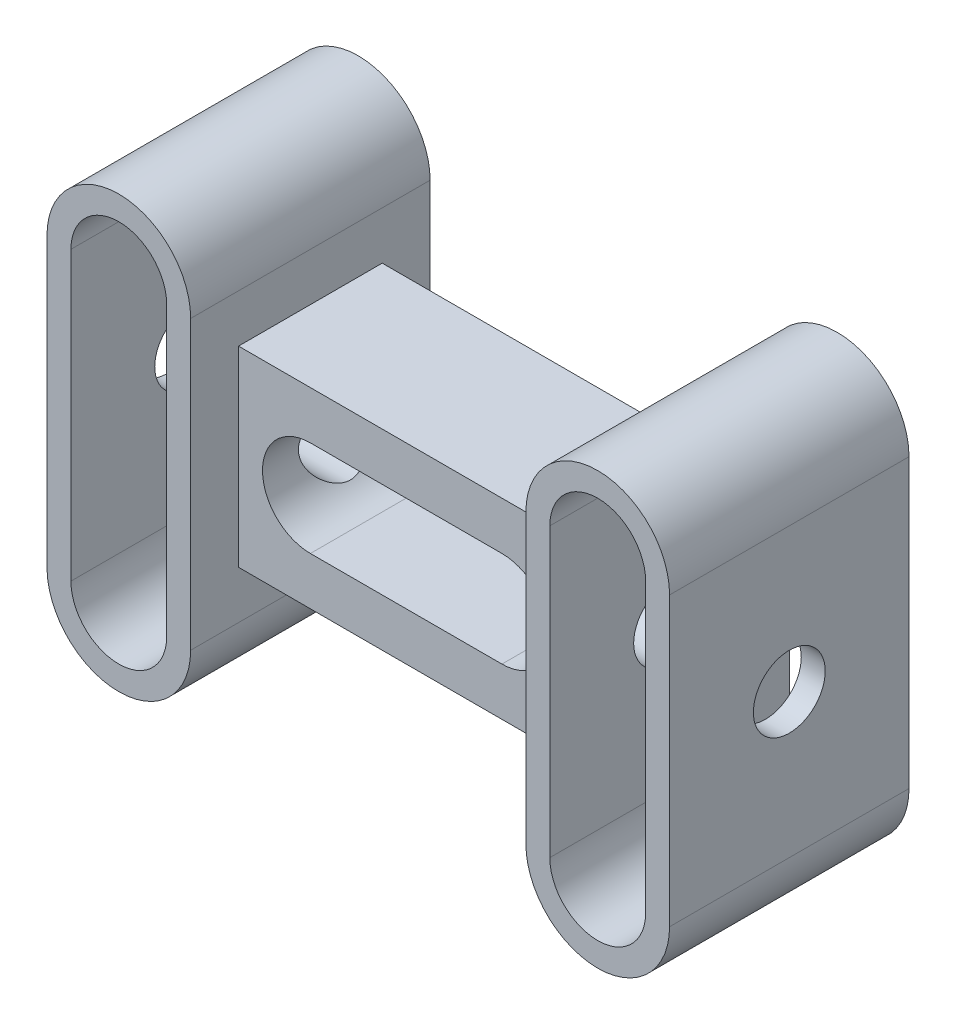
SolidWorks part; units mm, degrees
ref_plane "Front Plane" through (0, 0, 0) normal (0, 0, 1) x (1, 0, 0)
ref_plane "Top Plane" through (0, 0, 0) normal (0, 1, 0) x (1, 0, 0)
ref_plane "Right Plane" through (0, 0, 0) normal (1, 0, 0) x (0, 0, -1)
sketch "Sketch1" plane through (0, 0, 0) normal (0, 0, 1) x (1, 0, 0)
  line L0 (-50, 30) -> (-50, -30) construction
  line L1 (-35, 30) -> (-35, -30)
  line L2 (-65, 30) -> (-65, -30)
  line L3 (-50, 30) -> (-50, -30) construction
  line L4 (-40, 30) -> (-40, -30)
  line L5 (-60, 30) -> (-60, -30)
  line L6 (0, -55) -> (0, 55) construction
  line L7 (50, 30) -> (50, -30) construction
  line L8 (35, 30) -> (35, -30)
  line L9 (65, 30) -> (65, -30)
  line L10 (50, 30) -> (50, -30) construction
  line L11 (40, 30) -> (40, -30)
  line L12 (60, 30) -> (60, -30)
  arc A0 (-35, 30) -> (-65, 30) centre (-50, 30) ccw
  arc A1 (-65, -30) -> (-35, -30) centre (-50, -30) ccw
  arc A2 (-40, 30) -> (-60, 30) centre (-50, 30) ccw
  arc A3 (-60, -30) -> (-40, -30) centre (-50, -30) ccw
  arc A4 (35, 30) -> (65, 30) centre (50, 30) cw
  arc A5 (65, -30) -> (35, -30) centre (50, -30) cw
  arc A6 (40, 30) -> (60, 30) centre (50, 30) cw
  arc A7 (60, -30) -> (40, -30) centre (50, -30) cw
  point P2 (-50, 0)
  point P7 (-50, 0)
  point P14 (0, 0)
  point P20 (50, 0)
  point P27 (50, 0)
  dimension "D1" = 15
  dimension "D2" = 10
  dimension "D3" = 60
  dimension "D4" = 50
extrude "Boss-Extrude1" add sketch "Sketch1" along normal blind 25 and the other way blind 25
sketch "Sketch3" plane through (-35, 0, 0) normal (1, 0, 0) x (0, 0, -1)
  line L1 (-15, 20) -> (15, 20)
  line L2 (-15, 20) -> (-15, -20)
  line L3 (-15, -20) -> (15, -20)
  line L4 (15, 20) -> (15, -20)
  line L5 (-15, 20) -> (15, -20) construction
  line L6 (-15, -20) -> (15, 20) construction
  point P0 (0, 0)
  dimension "D1" = 30
  dimension "D2" = 40
extrude "Boss-Extrude2" add sketch "Sketch3" along normal up to next
sketch "Sketch4" plane through (0, 0, -15) normal (0, 0, -1) x (-1, 0, 0)
  line L0 (-20, 0) -> (20, 0) construction
  line L1 (-20, 10) -> (20, 10)
  line L2 (-20, -10) -> (20, -10)
  arc A0 (-20, 10) -> (-20, -10) centre (-20, 0) ccw
  arc A1 (20, -10) -> (20, 10) centre (20, 0) ccw
  point P3 (0, 0)
  point P8 (7.0399, 0)
  dimension "D1" = 20
  dimension "D2" = 40
extrude "Cut-Extrude1" cut sketch "Sketch4" against normal through all
hole_wizard "Hole1" positions "Sketch5" profile "Sketch6" legacy end condition through all
sketch "Sketch5" plane through (65, 0, 0) normal (1, 0, 0) x (0, 0, -1)
  point P0 (0, 0)
sketch "Sketch6" plane through (65, 0, 0) normal (0, 1, 0) x (0, 0, -1)
  line L0 (0, 0) -> (0, 130)
  line L1 (0, 130) -> (7.5, 130)
  line L2 (7.5, 130) -> (7.5, 0)
  line L3 (7.5, 0) -> (0, 0)
  line L4 (0, 110) -> (0, -10) construction
  dimension "Diameter" = 15
  dimension "Depth" = 130
